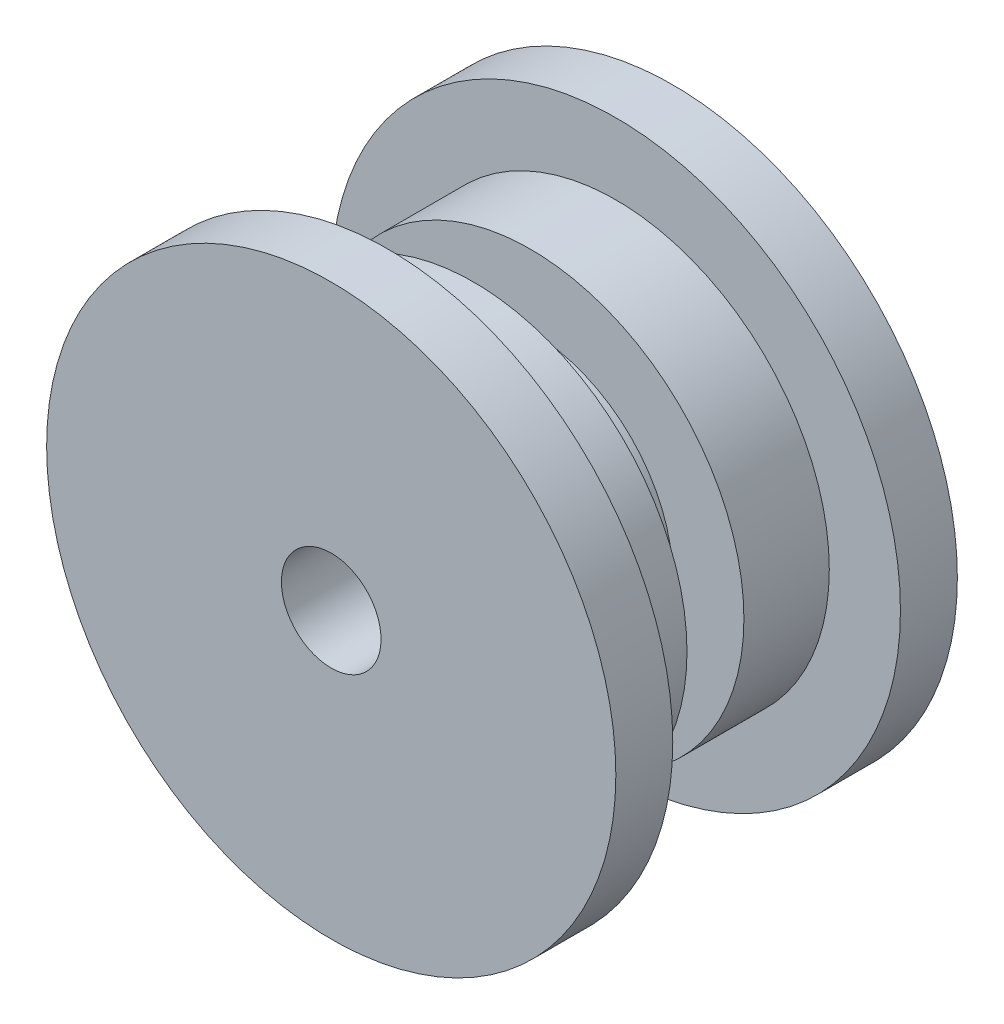
SolidWorks part; units mm, degrees
ref_plane "前视基准面" through (0, 0, 0) normal (0, 0, 1) x (1, 0, 0)
ref_plane "上视基准面" through (0, 0, 0) normal (0, 1, 0) x (1, 0, 0)
ref_plane "右视基准面" through (0, 0, 0) normal (1, 0, 0) x (0, 0, -1)
other "Configuration Table"
sketch "草图1" plane through (0, 0, 0) normal (0, 0, 1) x (1, 0, 0)
  circle A0 centre (0, 0) radius 10
  dimension "D1" = 20
extrude "凸台-拉伸1" add sketch "草图1" along normal blind 2
sketch "草图2" plane through (0, 0, 2) normal (0, 0, 1) x (1, 0, 0)
  circle A0 centre (0, 0) radius 7.5
  dimension "D1" = 15
extrude "凸台-拉伸2" add sketch "草图2" along normal blind 3
sketch "草图3" plane through (0, 0, 5) normal (0, 0, 1) x (1, 0, 0)
  circle A0 centre (0, 0) radius 5
  dimension "D1" = 10
extrude "凸台-拉伸3" add sketch "草图3" along normal blind 2
sketch "草图4" plane through (0, 0, 7) normal (0, 0, 1) x (1, 0, 0)
  circle A0 centre (0, 0) radius 7.5 construction
  circle A1 centre (0, 0) radius 7.5
extrude "凸台-拉伸4" add sketch "草图4" along normal blind 3
sketch "草图5" plane through (0, 0, 10) normal (0, 0, 1) x (1, 0, 0)
  circle A0 centre (0, 0) radius 10 construction
  circle A1 centre (0, 0) radius 10
extrude "凸台-拉伸5" add sketch "草图5" along normal blind 2
sketch "草图6" plane through (0, 0, 0) normal (0, 0, -1) x (-1, 0, 0)
  circle A0 centre (0, 0) radius 1.75
  dimension "D1" = 3.5
extrude "切除-拉伸1" cut sketch "草图6" against normal blind 22
